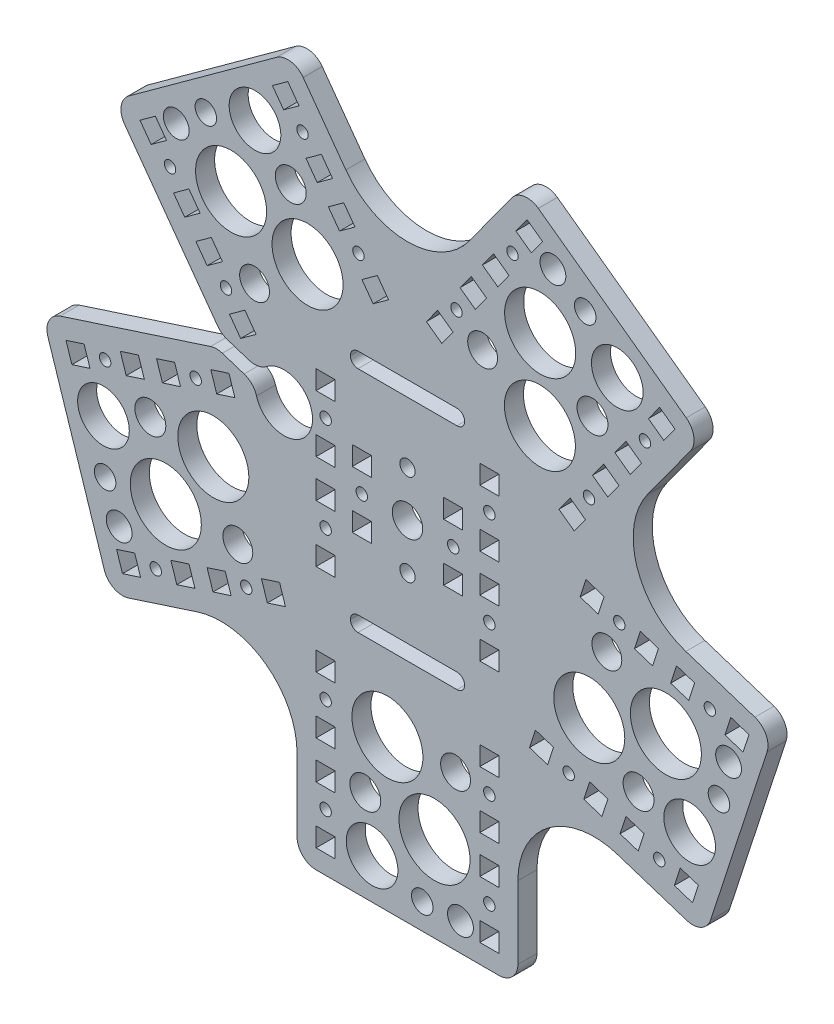
SolidWorks part; units mm, degrees
ref_plane "Plan de face" through (0, 0, 0) normal (0, 0, 1) x (1, 0, 0)
ref_plane "Plan de dessus" through (0, 0, 0) normal (0, 1, 0) x (1, 0, 0)
ref_plane "Plan de droite" through (0, 0, 0) normal (1, 0, 0) x (0, 0, -1)
sketch "Esquisse1" plane through (0, 0, 0) normal (0, 0, 1) x (1, 0, 0)
  line L0 (0, 0) -> (17.8582, 0) construction
  line L1 (-20, 40) -> (20, 40) construction
  line L2 (20, 40) -> (20, -40) construction
  line L3 (20, -40) -> (-20, -40) construction
  line L4 (-20, -40) -> (-20, 40) construction
  line L13 (0, 0) -> (0, 13.4404) construction
  line L16 (-20, -40) -> (-20, 40) construction
  line L18 (0, -40) -> (0, 40) construction
  line L19 (-15, -32) -> (-15, -28)
  line L20 (-15, 32) -> (15, 32)
  line L21 (-15, 32) -> (-15, 28)
  line L22 (-15, 28) -> (15, 28)
  line L23 (15, 32) -> (15, 28)
  line L24 (-15, -28) -> (15, -28)
  line L25 (15, -32) -> (15, -28)
  line L26 (-15, -32) -> (15, -32)
  line L27 (-29, -91.5) -> (29, -91.5)
  line L28 (29, -91.5) -> (29, -39.9151)
  line L29 (-29, -91.5) -> (-29, -39.9151)
  line L30 (-78.0602, -55.8557) -> (-29, -39.9151)
  line L31 (-95.9832, -0.6944) -> (-78.0602, -55.8557)
  line L32 (-95.9832, -0.6944) -> (-46.923, 15.2462) construction
  line L33 (-77.2438, 56.9793) -> (-46.923, 15.2462) construction
  line L34 (-30.3209, 91.0708) -> (-77.2438, 56.9793)
  line L35 (-30.3209, 91.0708) -> (0, 49.3377)
  line L36 (30.3209, 91.0708) -> (0, 49.3377)
  line L37 (77.2438, 56.9793) -> (30.3209, 91.0708)
  line L38 (77.2438, 56.9793) -> (46.923, 15.2462)
  line L39 (95.9832, -0.6944) -> (46.923, 15.2462)
  line L40 (78.0602, -55.8557) -> (95.9832, -0.6944)
  line L41 (78.0602, -55.8557) -> (29, -39.9151)
  line L42 (-15, 40) -> (15, 40) construction
  line L43 (-15, 40) -> (-15, 36) construction
  line L44 (-15, 36) -> (15, 36) construction
  line L45 (15, 40) -> (15, 36) construction
  line L46 (-15, -40) -> (-15, -36) construction
  line L47 (-15, -40) -> (15, -40) construction
  line L48 (15, -40) -> (15, -36) construction
  line L49 (-15, -36) -> (15, -36) construction
  line L50 (-77.2438, 56.9793) -> (-48.923, 17.999)
  line L51 (-48.923, 17.999) -> (-38.6965, 14.6762)
  line L52 (-38.6965, 14.6762) -> (-39.9326, 10.872) construction
  line L53 (-39.9326, 10.872) -> (-50.1591, 14.1947)
  line L54 (-50.1591, 14.1947) -> (-95.9832, -0.6944)
  line L55 (-46.923, 15.2462) -> (-39.3145, 12.7741) construction
  arc A0 (-38.6965, 14.6762) -> (-39.9326, 10.872) centre (-32.4399, 10.5404) cw
  circle A1 centre (0, 0) radius 4
  circle A2 centre (12, 0) radius 2 construction
  circle A3 centre (0, -12) radius 2
  circle A4 centre (-12, 0) radius 2 construction
  circle A5 centre (0, 12) radius 2
  circle A6 centre (-5.2713, -51.9057) radius 9.3306
  circle A7 centre (7.0906, -69.0484) radius 9.3306
  circle A8 centre (-9.3008, -80.9322) radius 6.7851
  circle A9 centre (-11.0766, -67.4093) radius 4.0624
  circle A10 centre (12.6227, -50.9495) radius 3.924
  circle A11 centre (3.8806, -84.7569) radius 2.83
  circle A12 centre (13.9204, -84.1422) radius 3.3916
  circle A13 centre (-75.7223, -39.2404) radius 3.3916
  circle A14 centre (-79.4094, -29.882) radius 2.83
  circle A15 centre (-79.8452, -16.1638) radius 6.7851
  circle A16 centre (-67.5329, -10.2962) radius 4.0624
  circle A17 centre (-50.9942, -11.0265) radius 9.3306
  circle A18 centre (-44.5553, -27.7492) radius 3.924
  circle A19 centre (-63.4778, -28.0807) radius 9.3306
  circle A20 centre (-60.7194, 59.8903) radius 3.3916
  circle A21 centre (-52.9583, 66.2888) radius 2.83
  circle A22 centre (-40.0462, 70.9424) radius 6.7851
  circle A23 centre (-30.661, 61.0459) radius 4.0624
  circle A24 centre (-26.2449, 45.091) radius 9.3306
  circle A25 centre (-40.1594, 33.7996) radius 3.924
  circle A26 centre (-46.3221, 51.6936) radius 9.3306
  circle A27 centre (38.1957, 76.2547) radius 3.3916
  circle A28 centre (46.6794, 70.8507) radius 2.83
  circle A29 centre (55.0953, 60.0086) radius 6.7851
  circle A30 centre (48.5833, 48.0246) radius 4.0624
  circle A31 centre (34.774, 38.8942) radius 9.3306
  circle A32 centre (19.7354, 48.6385) radius 3.924
  circle A33 centre (34.8492, 60.0291) radius 9.3306
  circle A34 centre (84.3256, -12.7623) radius 3.3916
  circle A35 centre (81.8078, -22.5006) radius 2.83
  circle A36 centre (74.097, -33.855) radius 6.7851
  circle A37 centre (60.6872, -31.3651) radius 4.0624
  circle A38 centre (47.7363, -21.053) radius 9.3306
  circle A39 centre (52.3565, -3.7394) radius 3.924
  circle A40 centre (67.8601, -14.5936) radius 9.3306
  point P12 (0, 0)
  point P19 (0, 0)
  point P32 (-37.6183, 51.7771)
  point P42 (0, 0)
  point P56 (0, 0)
  point P64 (0, 0)
  point P134 (0, 0)
  line B0 (-24, -71.5) -> (-24, -66.5)
  line B1 (-24, -71.5) -> (-19, -71.5)
  line B2 (-19, -71.5) -> (-19, -66.5)
  line B3 (-24, -66.5) -> (-19, -66.5)
  line B4 (-24, -81.5) -> (-24, -86.5)
  line B5 (-24, -81.5) -> (-19, -81.5)
  line B6 (-19, -81.5) -> (-19, -86.5)
  line B7 (-24, -86.5) -> (-19, -86.5)
  circle B8 centre (-21.5, -76.5) radius 1.5
  line B9 (-24, -56.5) -> (-24, -61.5)
  line B10 (-24, -56.5) -> (-19, -56.5)
  line B11 (-19, -56.5) -> (-19, -61.5)
  line B12 (-24, -61.5) -> (-19, -61.5)
  line B13 (-24, -46.5) -> (-24, -41.5)
  line B14 (-24, -46.5) -> (-19, -46.5)
  line B15 (-19, -46.5) -> (-19, -41.5)
  line B16 (-24, -41.5) -> (-19, -41.5)
  circle B17 centre (-21.5, -51.5) radius 1.5
  line B18 (24, -56.5) -> (24, -61.5)
  line B19 (24, -56.5) -> (19, -56.5)
  line B20 (19, -56.5) -> (19, -61.5)
  line B21 (24, -61.5) -> (19, -61.5)
  line B22 (24, -46.5) -> (24, -41.5)
  line B23 (24, -46.5) -> (19, -46.5)
  line B24 (19, -46.5) -> (19, -41.5)
  line B25 (24, -41.5) -> (19, -41.5)
  circle B26 centre (21.5, -51.5) radius 1.5
  line B27 (24, -71.5) -> (24, -66.5)
  line B28 (24, -71.5) -> (19, -71.5)
  line B29 (19, -71.5) -> (19, -66.5)
  line B30 (24, -66.5) -> (19, -66.5)
  line B31 (24, -81.5) -> (24, -86.5)
  line B32 (24, -81.5) -> (19, -81.5)
  line B33 (19, -81.5) -> (19, -86.5)
  line B34 (24, -86.5) -> (19, -86.5)
  circle B35 centre (21.5, -76.5) radius 1.5
  line B36 (24, -86.5) -> (-24, -86.5) construction
  line B37 (0, -86.5) -> (0, -41.5) construction
  line B38 (-75.4169, 0.7306) -> (-70.6617, 2.2757)
  line B39 (-75.4169, 0.7306) -> (-73.8719, -4.0246)
  line B40 (-73.8719, -4.0246) -> (-69.1166, -2.4796)
  line B41 (-70.6617, 2.2757) -> (-69.1166, -2.4796)
  line B42 (-84.9275, -2.3595) -> (-89.6828, -3.9046)
  line B43 (-84.9275, -2.3595) -> (-83.3824, -7.1148)
  line B44 (-83.3824, -7.1148) -> (-88.1377, -8.6599)
  line B45 (-89.6828, -3.9046) -> (-88.1377, -8.6599)
  circle B46 centre (-79.3997, -3.1921) radius 1.5
  line B47 (-61.1511, 5.3659) -> (-65.9064, 3.8208)
  line B48 (-61.1511, 5.3659) -> (-59.606, 0.6106)
  line B49 (-59.606, 0.6106) -> (-64.3613, -0.9345)
  line B50 (-65.9064, 3.8208) -> (-64.3613, -0.9345)
  line B51 (-51.6405, 8.4561) -> (-46.8853, 10.0012)
  line B52 (-51.6405, 8.4561) -> (-50.0955, 3.7008)
  line B53 (-50.0955, 3.7008) -> (-45.3402, 5.2459)
  line B54 (-46.8853, 10.0012) -> (-45.3402, 5.2459)
  circle B55 centre (-55.6233, 4.5333) radius 1.5
  line B56 (-46.3183, -40.2848) -> (-51.0736, -41.8299)
  line B57 (-46.3183, -40.2848) -> (-47.8634, -35.5295)
  line B58 (-47.8634, -35.5295) -> (-52.6187, -37.0746)
  line B59 (-51.0736, -41.8299) -> (-52.6187, -37.0746)
  line B60 (-36.8077, -37.1946) -> (-32.0524, -35.6496)
  line B61 (-36.8077, -37.1946) -> (-38.3528, -32.4394)
  line B62 (-38.3528, -32.4394) -> (-33.5975, -30.8943)
  line B63 (-32.0524, -35.6496) -> (-33.5975, -30.8943)
  circle B64 centre (-42.3355, -36.3621) radius 1.5
  line B65 (-60.5841, -44.9201) -> (-55.8289, -43.375)
  line B66 (-60.5841, -44.9201) -> (-62.1292, -40.1648)
  line B67 (-62.1292, -40.1648) -> (-57.3739, -38.6197)
  line B68 (-55.8289, -43.375) -> (-57.3739, -38.6197)
  line B69 (-70.0947, -48.0102) -> (-74.85, -49.5553)
  line B70 (-70.0947, -48.0102) -> (-71.6398, -43.255)
  line B71 (-71.6398, -43.255) -> (-76.3951, -44.8)
  line B72 (-74.85, -49.5553) -> (-76.3951, -44.8)
  circle B73 centre (-66.112, -44.0875) radius 1.5
  line B74 (-22.6102, 71.9516) -> (-19.6713, 67.9065)
  line B75 (-22.6102, 71.9516) -> (-26.6553, 69.0126)
  line B76 (-26.6553, 69.0126) -> (-23.7164, 64.9675)
  line B77 (-19.6713, 67.9065) -> (-23.7164, 64.9675)
  line B78 (-28.4881, 80.0417) -> (-31.427, 84.0868)
  line B79 (-28.4881, 80.0417) -> (-32.5332, 77.1028)
  line B80 (-32.5332, 77.1028) -> (-35.4721, 81.1479)
  line B81 (-31.427, 84.0868) -> (-35.4721, 81.1479)
  circle B82 centre (-27.5717, 74.5272) radius 1.5
  line B83 (-13.7935, 59.8163) -> (-16.7324, 63.8614)
  line B84 (-13.7935, 59.8163) -> (-17.8385, 56.8774)
  line B85 (-17.8385, 56.8774) -> (-20.7775, 60.9225)
  line B86 (-16.7324, 63.8614) -> (-20.7775, 60.9225)
  line B87 (-7.9156, 51.7261) -> (-4.9767, 47.6811)
  line B88 (-7.9156, 51.7261) -> (-11.9607, 48.7872)
  line B89 (-11.9607, 48.7872) -> (-9.0218, 44.7421)
  line B90 (-4.9767, 47.6811) -> (-9.0218, 44.7421)
  circle B91 centre (-12.8771, 54.3018) radius 1.5
  line B92 (-52.6263, 31.6026) -> (-55.5652, 35.6477)
  line B93 (-52.6263, 31.6026) -> (-48.5812, 34.5415)
  line B94 (-48.5812, 34.5415) -> (-51.5201, 38.5866)
  line B95 (-55.5652, 35.6477) -> (-51.5201, 38.5866)
  line B96 (-46.7484, 23.5124) -> (-43.8095, 19.4674)
  line B97 (-46.7484, 23.5124) -> (-42.7033, 26.4514)
  line B98 (-42.7033, 26.4514) -> (-39.7644, 22.4063)
  line B99 (-43.8095, 19.4674) -> (-39.7644, 22.4063)
  circle B100 centre (-47.6648, 29.027) radius 1.5
  line B101 (-61.4431, 43.7379) -> (-58.5041, 39.6928)
  line B102 (-61.4431, 43.7379) -> (-57.398, 46.6768)
  line B103 (-57.398, 46.6768) -> (-54.459, 42.6317)
  line B104 (-58.5041, 39.6928) -> (-54.459, 42.6317)
  line B105 (-67.3209, 51.828) -> (-70.2598, 55.8731)
  line B106 (-67.3209, 51.828) -> (-63.2758, 54.767)
  line B107 (-63.2758, 54.767) -> (-66.2147, 58.8121)
  line B108 (-70.2598, 55.8731) -> (-66.2147, 58.8121)
  circle B109 centre (-62.3594, 49.2524) radius 1.5
  line B110 (61.4431, 43.7379) -> (58.5041, 39.6928)
  line B111 (61.4431, 43.7379) -> (57.398, 46.6768)
  line B112 (57.398, 46.6768) -> (54.459, 42.6317)
  line B113 (58.5041, 39.6928) -> (54.459, 42.6317)
  line B114 (67.3209, 51.828) -> (70.2598, 55.8731)
  line B115 (67.3209, 51.828) -> (63.2758, 54.767)
  line B116 (63.2758, 54.767) -> (66.2147, 58.8121)
  line B117 (70.2598, 55.8731) -> (66.2147, 58.8121)
  circle B118 centre (62.3594, 49.2524) radius 1.5
  line B119 (52.6263, 31.6026) -> (55.5652, 35.6477)
  line B120 (52.6263, 31.6026) -> (48.5812, 34.5415)
  line B121 (48.5812, 34.5415) -> (51.5201, 38.5866)
  line B122 (55.5652, 35.6477) -> (51.5201, 38.5866)
  line B123 (46.7484, 23.5124) -> (43.8095, 19.4674)
  line B124 (46.7484, 23.5124) -> (42.7033, 26.4514)
  line B125 (42.7033, 26.4514) -> (39.7644, 22.4063)
  line B126 (43.8095, 19.4674) -> (39.7644, 22.4063)
  circle B127 centre (47.6648, 29.027) radius 1.5
  line B128 (13.7935, 59.8163) -> (16.7324, 63.8614)
  line B129 (13.7935, 59.8163) -> (17.8385, 56.8774)
  line B130 (17.8385, 56.8774) -> (20.7775, 60.9225)
  line B131 (16.7324, 63.8614) -> (20.7775, 60.9225)
  line B132 (7.9156, 51.7261) -> (4.9767, 47.6811)
  line B133 (7.9156, 51.7261) -> (11.9607, 48.7872)
  line B134 (11.9607, 48.7872) -> (9.0218, 44.7421)
  line B135 (4.9767, 47.6811) -> (9.0218, 44.7421)
  circle B136 centre (12.8771, 54.3018) radius 1.5
  line B137 (22.6102, 71.9516) -> (19.6713, 67.9065)
  line B138 (22.6102, 71.9516) -> (26.6553, 69.0126)
  line B139 (26.6553, 69.0126) -> (23.7164, 64.9675)
  line B140 (19.6713, 67.9065) -> (23.7164, 64.9675)
  line B141 (28.4881, 80.0417) -> (31.427, 84.0868)
  line B142 (28.4881, 80.0417) -> (32.5332, 77.1028)
  line B143 (32.5332, 77.1028) -> (35.4721, 81.1479)
  line B144 (31.427, 84.0868) -> (35.4721, 81.1479)
  circle B145 centre (27.5717, 74.5272) radius 1.5
  line B146 (60.5841, -44.9201) -> (55.8289, -43.375)
  line B147 (60.5841, -44.9201) -> (62.1292, -40.1648)
  line B148 (62.1292, -40.1648) -> (57.3739, -38.6197)
  line B149 (55.8289, -43.375) -> (57.3739, -38.6197)
  line B150 (70.0947, -48.0102) -> (74.85, -49.5553)
  line B151 (70.0947, -48.0102) -> (71.6398, -43.255)
  line B152 (71.6398, -43.255) -> (76.3951, -44.8)
  line B153 (74.85, -49.5553) -> (76.3951, -44.8)
  circle B154 centre (66.112, -44.0875) radius 1.5
  line B155 (46.3183, -40.2848) -> (51.0736, -41.8299)
  line B156 (46.3183, -40.2848) -> (47.8634, -35.5295)
  line B157 (47.8634, -35.5295) -> (52.6187, -37.0746)
  line B158 (51.0736, -41.8299) -> (52.6187, -37.0746)
  line B159 (36.8077, -37.1946) -> (32.0524, -35.6496)
  line B160 (36.8077, -37.1946) -> (38.3528, -32.4394)
  line B161 (38.3528, -32.4394) -> (33.5975, -30.8943)
  line B162 (32.0524, -35.6496) -> (33.5975, -30.8943)
  circle B163 centre (42.3355, -36.3621) radius 1.5
  line B164 (61.1511, 5.3659) -> (65.9064, 3.8208)
  line B165 (61.1511, 5.3659) -> (59.606, 0.6106)
  line B166 (59.606, 0.6106) -> (64.3613, -0.9345)
  line B167 (65.9064, 3.8208) -> (64.3613, -0.9345)
  line B168 (51.6405, 8.4561) -> (46.8853, 10.0012)
  line B169 (51.6405, 8.4561) -> (50.0955, 3.7008)
  line B170 (50.0955, 3.7008) -> (45.3402, 5.2459)
  line B171 (46.8853, 10.0012) -> (45.3402, 5.2459)
  circle B172 centre (55.6233, 4.5333) radius 1.5
  line B173 (75.4169, 0.7306) -> (70.6617, 2.2757)
  line B174 (75.4169, 0.7306) -> (73.8719, -4.0246)
  line B175 (73.8719, -4.0246) -> (69.1166, -2.4796)
  line B176 (70.6617, 2.2757) -> (69.1166, -2.4796)
  line B177 (84.9275, -2.3595) -> (89.6828, -3.9046)
  line B178 (84.9275, -2.3595) -> (83.3824, -7.1148)
  line B179 (83.3824, -7.1148) -> (88.1377, -8.6599)
  line B180 (89.6828, -3.9046) -> (88.1377, -8.6599)
  circle B181 centre (79.3997, -3.1921) radius 1.5
  line B182 (-24, -7.5) -> (-24, -2.5)
  line B183 (-24, -7.5) -> (-19, -7.5)
  line B184 (-19, -7.5) -> (-19, -2.5)
  line B185 (-24, -2.5) -> (-19, -2.5)
  line B186 (-24, -17.5) -> (-24, -22.5)
  line B187 (-24, -17.5) -> (-19, -17.5)
  line B188 (-19, -17.5) -> (-19, -22.5)
  line B189 (-24, -22.5) -> (-19, -22.5)
  circle B190 centre (-21.5, -12.5) radius 1.5
  line B191 (-24, 7.5) -> (-24, 2.5)
  line B192 (-24, 7.5) -> (-19, 7.5)
  line B193 (-19, 7.5) -> (-19, 2.5)
  line B194 (-24, 2.5) -> (-19, 2.5)
  line B195 (-24, 17.5) -> (-24, 22.5)
  line B196 (-24, 17.5) -> (-19, 17.5)
  line B197 (-19, 17.5) -> (-19, 22.5)
  line B198 (-24, 22.5) -> (-19, 22.5)
  circle B199 centre (-21.5, 12.5) radius 1.5
  line B200 (24, 7.5) -> (24, 2.5)
  line B201 (24, 7.5) -> (19, 7.5)
  line B202 (19, 7.5) -> (19, 2.5)
  line B203 (24, 2.5) -> (19, 2.5)
  line B204 (24, 17.5) -> (24, 22.5)
  line B205 (24, 17.5) -> (19, 17.5)
  line B206 (19, 17.5) -> (19, 22.5)
  line B207 (24, 22.5) -> (19, 22.5)
  circle B208 centre (21.5, 12.5) radius 1.5
  line B209 (24, -7.5) -> (24, -2.5)
  line B210 (24, -7.5) -> (19, -7.5)
  line B211 (19, -7.5) -> (19, -2.5)
  line B212 (24, -2.5) -> (19, -2.5)
  line B213 (24, -17.5) -> (24, -22.5)
  line B214 (24, -17.5) -> (19, -17.5)
  line B215 (19, -17.5) -> (19, -22.5)
  line B216 (24, -22.5) -> (19, -22.5)
  circle B217 centre (21.5, -12.5) radius 1.5
  line B218 (24, 22.5) -> (-24, 22.5) construction
  line B219 (24, -22.5) -> (-24, -22.5) construction
  line B220 (0, -22.5) -> (0, 22.5) construction
  line B221 (14.5, -5) -> (14.5, -10)
  line B222 (14.5, -5) -> (9.5, -5)
  line B223 (9.5, -5) -> (9.5, -10)
  line B224 (14.5, -10) -> (9.5, -10)
  line B225 (14.5, 5) -> (14.5, 10)
  line B226 (14.5, 5) -> (9.5, 5)
  line B227 (9.5, 5) -> (9.5, 10)
  line B228 (14.5, 10) -> (9.5, 10)
  line B229 (12, 0) -> (18.2802, 0) construction
  circle B230 centre (12, 0) radius 1.5
  line B231 (-12, -5) -> (-12, 5) construction
  line B232 (-9.5, -5) -> (-9.5, -10)
  line B233 (-9.5, -5) -> (-14.5, -5)
  line B234 (-14.5, -5) -> (-14.5, -10)
  line B235 (-9.5, -10) -> (-14.5, -10)
  line B236 (-9.5, 5) -> (-9.5, 10)
  line B237 (-9.5, 5) -> (-14.5, 5)
  line B238 (-14.5, 5) -> (-14.5, 10)
  line B239 (-9.5, 10) -> (-14.5, 10)
  line B240 (-12, 0) -> (-5.7198, 0) construction
  circle B241 centre (-12, 0) radius 1.5
  dimension "D2" = 5
  dimension "D9" = 4
  dimension "D14" = 7.5
  dimension "D17" = 8
  dimension "D18" = 4
  dimension "D4" = 8
  dimension "D5" = 5
  dimension "D6" = 5
  dimension "D7" = 4
  dimension "D8" = 20
  dimension "D10" = 5
  dimension "D11" = 4
  dimension "D12" = 5
  dimension "D3" = 5
  dimension "D13" = 64
  dimension "D15" = 8
  dimension "D16" = 28
  dimension "D19" = 12
  dimension "D20" = 4
  dimension "D21" = 5
sketch_block_instance "Bloc1-4"
sketch_block "Bloc1"
sketch_block_instance "Trou M3 plots 5mm-54"
sketch_block "Trou M3 plots 5mm" parameters "D2"=3, "D1"=5, "D3"=5, "D4"=8
sketch_block_instance "Trou M3 plots 5mm-56"
sketch_block_instance "Trou M3 plots 5mm-55"
sketch_block_instance "Trou M3 plots 5mm-52"
sketch_block_instance "Bloc1-5"
sketch_block_instance "Bloc1-6"
sketch_block_instance "Bloc1-7"
sketch_block_instance "Bloc1-8"
sketch_block_instance "Bloc1-10"
sketch_block_instance "Trou M3 plots 5mm-61"
sketch_block_instance "Trou M3 plots 5mm-62"
extrude "Boss.-Extru.1" add sketch "Esquisse1" along normal blind 5
fillet "Congé1" radius 2 8 edges at (-15, -32, 2.5) (-15, -28, 2.5) (15, -28, 2.5) (15, -32, 2.5) (15, 28, 2.5) (15, 32, 2.5) (-15, 28, 2.5) (-15, 32, 2.5)
fillet "Congé2" radius 20 4 edges at (29, -39.9151, 2.5) (-29, -39.9151, 2.5) (0, 49.3377, 2.5) (46.923, 15.2462, 2.5)
fillet "Congé3" radius 5 14 edges at (-78.0602, -55.8557, 2.5) (-29, -91.5, 2.5) (29, -91.5, 2.5) (-30.3209, 91.0708, 2.5) (78.0602, -55.8557, 2.5) (95.9832, -0.6944, 2.5) (77.2438, 56.9793, 2.5) (30.3209, 91.0708, 2.5) (-48.923, 17.999, 2.5) (-50.1591, 14.1947, 2.5) (-39.9326, 10.872, 2.5) (-38.6965, 14.6762, 2.5) (-95.9832, -0.6944, 2.5) (-77.2438, 56.9793, 2.5)
